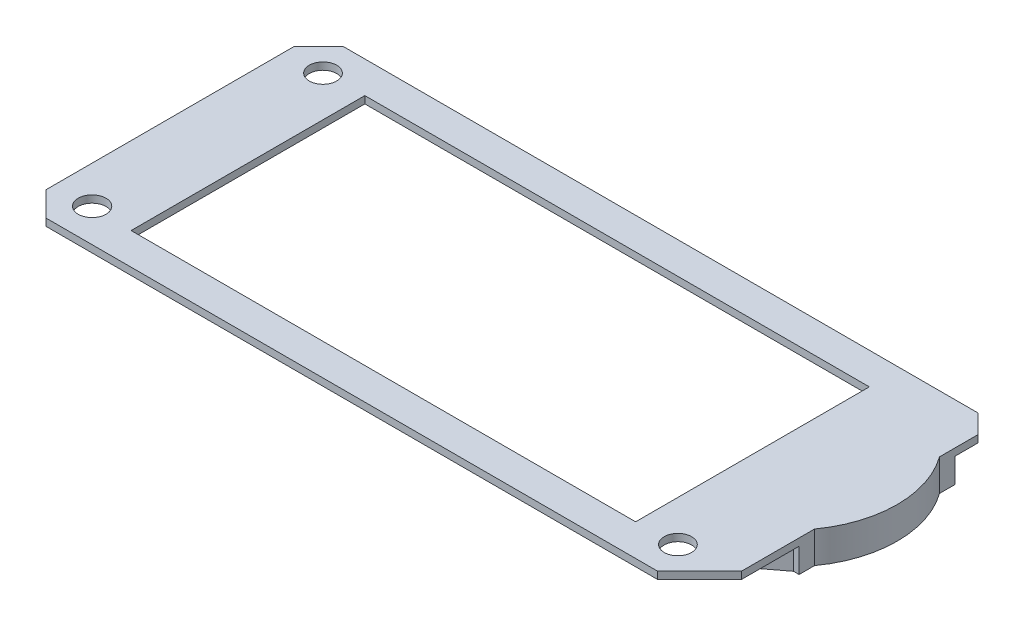
SolidWorks part; units mm, degrees
ref_plane "Спереди" through (0, 0, 0) normal (0, 0, 1) x (1, 0, 0)
ref_plane "Сверху" through (0, 0, 0) normal (0, 1, 0) x (1, 0, 0)
ref_plane "Справа" through (0, 0, 0) normal (1, 0, 0) x (0, 0, -1)
other "Configuration Table"
sketch "Эскиз1" plane through (0, 0, 0) normal (0, 1, 0) x (1, 0, 0)
  line L0 (22.2882, 7.8559) -> (22.2882, 6.5872)
  line L1 (16.2555, 8.9559) -> (16.2555, -8.4441)
  line L2 (22.2882, -3.3441) -> (22.2882, -2.0754)
  line L3 (-19.9118, 7.2559) -> (-19.9118, 8.9559)
  line L4 (-19.9118, -8.4441) -> (16.2555, -8.4441)
  line L5 (-19.9118, -8.4441) -> (-19.9118, -6.7441)
  line L6 (-19.9118, 8.9559) -> (16.2555, 8.9559)
  line L7 (16.2555, -8.4441) -> (16.2555, 8.9559)
  line L9 (15.6555, 8.3559) -> (-19.3118, 8.3559)
  line L10 (15.6555, 8.3559) -> (15.6555, -7.8441)
  line L11 (15.6555, -7.8441) -> (-19.3118, -7.8441)
  line L12 (-19.3118, 8.3559) -> (-19.3118, -7.8441)
  line L14 (22.2882, 7.6559) -> (21.9311, 7.6559)
  line L15 (21.9311, 7.6559) -> (20.4322, 8.8559)
  line L16 (20.4322, 8.8559) -> (18.4882, 8.8559)
  line L17 (18.4882, 8.8559) -> (18.4882, 7.8886)
  line L18 (18.4882, 7.8886) -> (16.2555, 8.2586)
  line L19 (16.2555, -4.5441) -> (19.0285, -4.5441)
  line L20 (19.0285, -4.5441) -> (19.0285, -5.5441)
  line L21 (19.0285, -5.5441) -> (19.9285, -5.5441)
  line L22 (19.9285, -5.5441) -> (19.9285, -4.6449)
  line L23 (21.9012, -3.1441) -> (19.9285, -4.6449)
  line L24 (22.2882, -3.1441) -> (21.9012, -3.1441)
  line L25 (20.9882, 10.5559) -> (-23.0118, 10.5559)
  line L26 (-23.0118, 10.5559) -> (-24.7118, 8.8559)
  line L27 (-24.7118, 8.8559) -> (-24.7118, -8.3441)
  line L28 (-24.7118, -8.3441) -> (-23.0118, -10.0441)
  line L29 (-23.0118, -10.0441) -> (19.3882, -10.0441)
  line L30 (19.3882, -10.0441) -> (22.2882, -7.1441)
  line L31 (22.2882, -7.1441) -> (22.2882, -3.3441)
  line L32 (16.2555, -8.4441) -> (-19.9118, -8.4441)
  line L33 (-19.9118, -8.4441) -> (-19.9118, -6.7441)
  line L34 (-19.9118, -6.7441) -> (-20.7118, -5.9441)
  line L35 (-20.7118, -5.9441) -> (-20.7118, 6.4559)
  line L36 (-20.7118, 6.4559) -> (-19.9118, 7.2559)
  line L37 (-19.9118, 7.2559) -> (-19.9118, 8.9559)
  line L38 (-19.9118, 8.9559) -> (16.2555, 8.9559)
  line L39 (22.2882, 7.8559) -> (22.2882, 9.2559)
  line L40 (22.2882, 9.2559) -> (20.9882, 10.5559)
  arc A0 (22.2882, -2.0754) -> (22.2882, 6.5872) centre (16.2882, 2.2559) ccw
  point P17 (0, 0)
  point P18 (0, 0)
  point P19 (0, 0)
  point P21 (0, 0)
  dimension "D1" = 7.4
  dimension "D2" = 0.6
  dimension "D3" = 0.6
  dimension "D4" = 0.6
  dimension "D5" = 0.6
  dimension "D7" = 6.0327
  dimension "D8" = 47
extrude "Бобышка-Вытянуть1" add sketch "Эскиз1" along normal blind 0.5 contours L39 L40 L25 L26 L27 L28 L29 L30 L31 L2 L24 L23 L22 L21 L20 L19 L1 L32 L33 L34 L35 L36 L37 L38 L18 L17 L16 L15 L14 L0 | L2 A0 L0 L14 L15 L16 L17 L18 L1 L19 L20 L21 L22 L23 L24 | L36 L35 L34 L5 L4 L1 L7 L6 L3 L12 L9 L10 L11 region at (22.2369, 0, -7.7559) region at (19.5729, 0, -1.9948) region at (15.8469, 0, -1.8573)
extrude "Бобышка-Вытянуть2" add sketch "Эскиз1<3>" against normal blind 1.7 contours L2 A0 L0 L14 L15 L16 L17 L18 L1 L19 L20 L21 L22 L23 L24 region at (19.5729, 0, -1.9948)
sketch "Эскиз1<3>" plane through (0, 0, 0) normal (0, 1, 0) x (1, 0, 0) same geometry as "Эскиз1"
sketch "Эскиз2" plane through (0, 0, 0) normal (0, 1, 0) x (1, 0, 0)
  line L0 (20.9882, 10.5559) -> (-23.0118, 10.5559) construction
  line L1 (-24.7118, 8.8559) -> (-24.7118, -8.3441) construction
  circle A0 centre (-22.1118, 8.2559) radius 0.95
  circle A1 centre (-22.1237, -7.7369) radius 0.9639
  circle A2 centre (18.4882, -7.7441) radius 0.95
  point P8 (0, 0)
  point P51 (0, 0)
  dimension "D1" = 15.9928
  dimension "D2" = 40.6119
  dimension "D3" = 111.466
  dimension "D4" = 2.3
  dimension "D5" = 2.6
extrude "Вырез-Вытянуть4" cut sketch "Эскиз2" along normal through all contours A0 | A1 | A2
